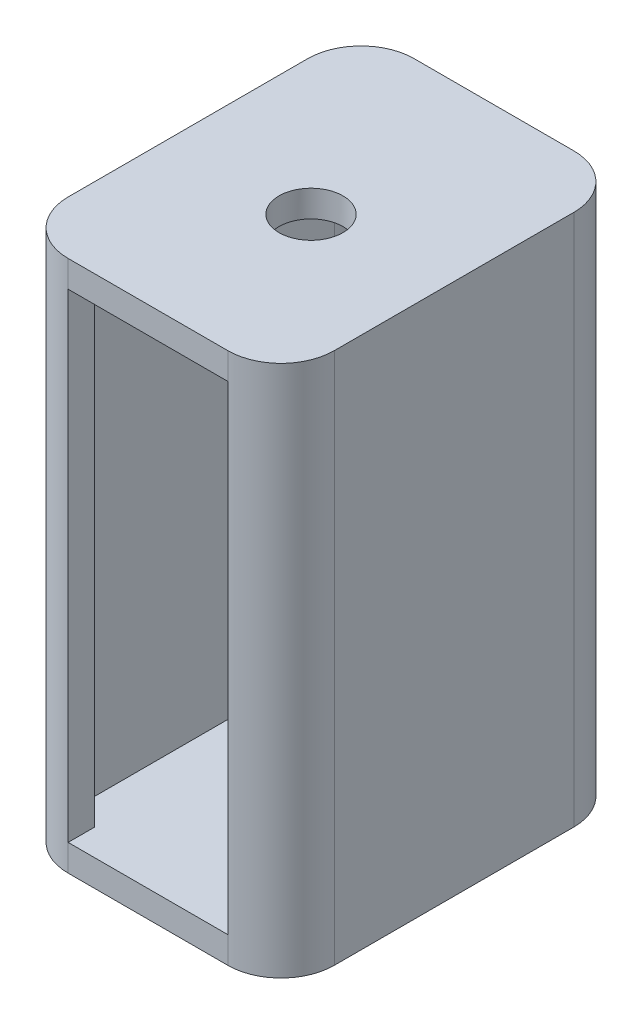
SolidWorks part; units mm, degrees
ref_plane "Alzado" through (0, 0, 0) normal (0, 0, 1) x (1, 0, 0)
ref_plane "Planta" through (0, 0, 0) normal (0, 1, 0) x (1, 0, 0)
ref_plane "Vista lateral" through (0, 0, 0) normal (1, 0, 0) x (0, 0, -1)
sketch "Croquis1" plane through (0, 0, 0) normal (1, 0, 0) x (0, 0, -1)
  line L1 (0, 0) -> (65, 0)
  line L2 (0, 0) -> (0, 100)
  line L3 (0, 100) -> (65, 100)
  line L4 (65, 0) -> (65, 100)
  dimension "D1" = 100
  dimension "D2" = 65
extrude "Saliente-Extruir1" add sketch "Croquis1" along normal blind 50
fillet "Redondeo1" radius 10 4 edges at (0, 50, 0) (50, 50, 0) (50, 50, -65) (0, 50, -65)
shell "Vaciado1" thickness 5 removed face at (25, 50, 0)
sketch "Croquis3" plane through (0, 100, 0) normal (0, 1, 0) x (1, 0, 0)
  line L0 (40, 0) -> (10, 0) construction
  circle A0 centre (25.6239, 30) radius 6
  dimension "D1" = 12
  dimension "D2" = 30
extrude "Cortar-Extruir1" cut sketch "Croquis3" against normal through all
